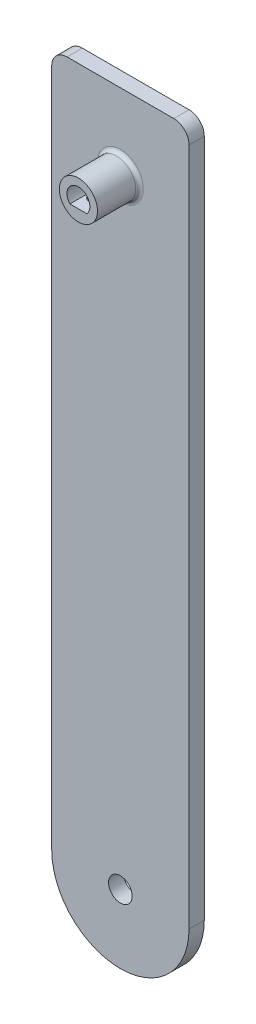
SolidWorks part; units mm, degrees
material "ABS"
ref_plane "Front Plane" through (0, 0, 0) normal (0, 0, 1) x (1, 0, 0)
ref_plane "Top Plane" through (0, 0, 0) normal (0, 1, 0) x (1, 0, 0)
ref_plane "Right Plane" through (0, 0, 0) normal (1, 0, 0) x (0, 0, -1)
sketch "Sketch1" plane through (0, 0, 0) normal (0, 0, 1) x (1, 0, 0)
  line L0 (0, 40) -> (0, -42.75) construction
  line L1 (9, -50) -> (-9, -50)
  line L2 (9, -50) -> (9, 50)
  line L3 (9, 50) -> (-9, 50)
  line L4 (-9, -50) -> (-9, 50)
  line L5 (1.118, 39) -> (-1.118, 39)
  arc A1 (1.118, 39) -> (-1.118, 39) centre (0, 40) ccw
  point P10 (-1.118, 39.0533)
  dimension "D5" = 1
  dimension "D6" = 10
  dimension "D7" = 3
  dimension "D1" = 18
  dimension "D2" = 100
  dimension "D3" = 9
  dimension "D4" = 50
extrude "Boss-Extrude1" add sketch "Sketch1" along normal blind 1 and the other way blind 1
sketch "Sketch2" plane through (0, 0, 1) normal (0, 0, 1) x (1, 0, 0)
  line L1 (-1.118, 39) -> (1.118, 39)
  circle A7 centre (0, 40) radius 2.5
  arc A8 (1.118, 39) -> (-1.118, 39) centre (0, 40) ccw
  arc A9 (1.118, 39) -> (-1.118, 39) centre (0, 40) ccw construction
  dimension "D1" = 5
extrude "Boss-Extrude2" add sketch "Sketch2" along normal blind 5.5
fillet "Fillet1" radius 0.5 1 edges at (2.5, 40, 1)
fillet "Fillet2" radius 2 2 edges at (-9, 50, 0) (9, 50, 0)
sketch "Sketch3" plane through (0, 0, 0) normal (0, 1, 0) x (1, 0, 0)
  line L2 (-2.5, -6.5) -> (2.5, -6.5) construction
  circle A0 centre (0, -4) radius 1
  point P6 (-1.6243, -6.5)
  point P9 (-1.5, -6.5)
  dimension "D1" = 2
  dimension "D2" = 2.5
extrude "Cut-Extrude1" cut sketch "Sketch3" along normal up to next
sketch "Sketch4" plane through (0, 0, -1) normal (0, 0, -1) x (-1, 0, 0)
  line L0 (9, 48) -> (9, -50) construction
  line L1 (9, -50) -> (-9, -50) construction
  circle A0 centre (0, -41) radius 1.55
  dimension "D1" = 3.1
  dimension "D2" = 9
  dimension "D3" = 9
extrude "Cut-Extrude2" cut sketch "Sketch4" against normal through all both and the other way through all
fillet "Fillet3" radius 9 2 edges at (-9, -50, 0) (9, -50, 0)
